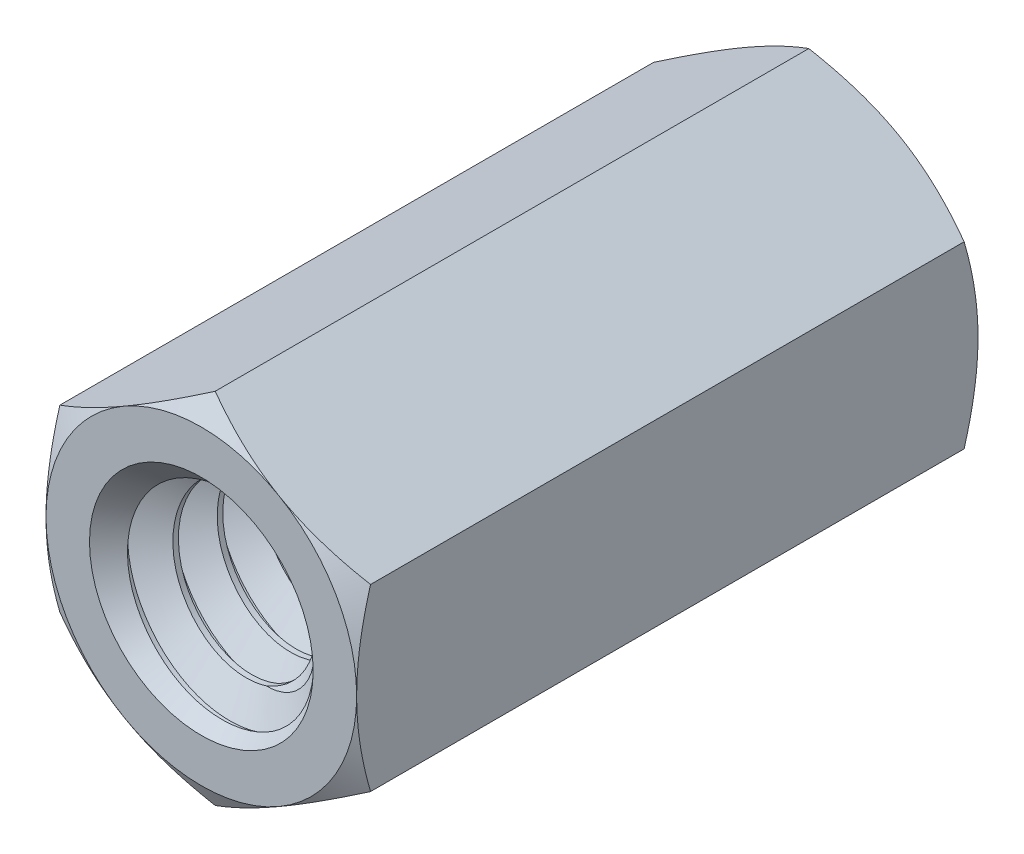
SolidWorks part; units mm, degrees
ref_plane "Front Plane" through (0, 0, 0) normal (0, 0, 1) x (1, 0, 0)
ref_plane "Top Plane" through (0, 0, 0) normal (0, 1, 0) x (1, 0, 0)
ref_plane "Right Plane" through (0, 0, 0) normal (1, 0, 0) x (0, 0, -1)
sketch "Sketch3" plane through (0, 0, 0) normal (1, 0, 0) x (0, 0, -1)
  line L0 (-3.175, 0) -> (3.175, 0) construction
  line L1 (0, 1.5875) -> (0, -1.5875) construction
  line L2 (-3.175, 1.0922) -> (-3.175, -1.0922) construction
  point P2 (-12.7, 0)
  point P3 (12.7, 0)
  dimension "Length" = 6.35
  dimension "Min Thread Length" = 15.875
  dimension "D1" = 15.875
  dimension "Thread Dia" = 2.1844
  dimension "Hex" = 3.175
sketch "Sketch1" plane through (0, 0, 0) normal (0, 0, 1) x (1, 0, 0)
  line L1 (0, 1.8331) -> (-1.5875, 0.9165)
  line L2 (-1.5875, 0.9165) -> (-1.5875, -0.9165)
  line L3 (-1.5875, -0.9165) -> (0, -1.8331)
  line L4 (0, -1.8331) -> (1.5875, -0.9165)
  line L5 (1.5875, -0.9165) -> (1.5875, 0.9165)
  line L6 (1.5875, 0.9165) -> (0, 1.8331)
  circle A0 centre (0, 0) radius 1.5875 construction
  circle A1 centre (0, 0) radius 1.0922
extrude "Extrude1" add sketch "Sketch1" along normal up to vertex (3.175 mm away) and the other way up to vertex (3.175 mm away) up to point (0, 0, 3.175) other way up to point (0, 0, -3.175)
sketch "Sketch11" plane through (0, 0, -3.175) normal (0, 0, -1) x (-1, 0, 0)
  circle A0 centre (0, 0) radius 1.0922 construction
  circle A1 centre (0, 0) radius 1.0922
curve "Helix/Spiral1" pitch 0.4536 height 6.8036 radius 1.0922 centre (0, 0, -3.175) axis (0, 0, 1) start towards (0, 1, 0) parameters "Pitch"=0.4536
sketch "Sketch12" plane through (0, 0, 0) normal (1, 0, 0) x (0, 0, -1)
  line L0 (3.5719, 1.0922) -> (3.175, 1.0922)
  line L1 (3.5719, 1.0922) -> (3.4018, 0.7976)
  line L2 (3.4018, 0.7976) -> (3.3451, 0.7976)
  line L3 (3.3451, 0.7976) -> (3.175, 1.0922)
  line L4 (3.3734, 0.7976) -> (3.3734, 1.0922) construction
  line L5 (3.4868, 0.9449) -> (3.26, 0.9449) construction
  dimension "D1" = 0.0567
  dimension "D2" = 0.2268
  dimension "D3" = 60
sweep "Sweep1" add profiles "Sketch12" path "Helix/Spiral1"
sketch "Sketch6" plane through (0, 0, -3.175) normal (0, 0, -1) x (-1, 0, 0)
  line L6 (0, 1.8331) -> (-1.5875, 0.9165)
  line L7 (-1.5875, 0.9165) -> (-1.5875, -0.9165)
  line L8 (-1.5875, -0.9165) -> (0, -1.8331)
  line L9 (0, -1.8331) -> (1.5875, -0.9165)
  line L10 (1.5875, -0.9165) -> (1.5875, 0.9165)
  line L11 (1.5875, 0.9165) -> (0, 1.8331)
  line L12 (0, 1.8331) -> (-1.5875, 0.9165)
  line L13 (-1.5875, 0.9165) -> (-1.5875, -0.9165)
  line L14 (-1.5875, -0.9165) -> (0, -1.8331)
  line L15 (0, -1.8331) -> (1.5875, -0.9165)
  line L16 (1.5875, -0.9165) -> (1.5875, 0.9165)
  line L17 (1.5875, 0.9165) -> (0, 1.8331)
  dimension "D1" = 0
extrude "Extrude2" cut sketch "Sketch6" along normal through all
sketch "Sketch7" plane through (0, 0, -3.175) normal (0, 0, -1) x (-1, 0, 0)
  circle A2 centre (0, 0) radius 1.143
  circle A3 centre (0, 0) radius 1.143
  dimension "D1" = 0.0508
extrude "Extrude3" cut sketch "Sketch7" against normal through all draft 43
sketch "Sketch8" plane through (0, 0, -3.175) normal (0, 0, -1) x (-1, 0, 0)
  circle A0 centre (0, 0) radius 1.5875 construction
  circle A1 centre (0, 0) radius 1.5875
extrude "Extrude4" cut sketch "Sketch8" against normal through all draft 60 flip side to cut
mirror "Mirror1" about plane through (0, 0, 0) normal (0, 0, 1) of "Extrude2", "Extrude3", "Extrude4"
sketch "Sketch9" [suppressed] plane through (0, 0, 0) normal (1, 0, 0) x (0, 0, -1)
  line L1 (-22.225, 3.2258) -> (22.225, 3.2258)
  line L2 (-22.225, 3.2258) -> (-22.225, 0)
  line L3 (-22.225, 0) -> (22.225, 0)
  line L4 (22.225, 3.2258) -> (22.225, 0)
  line L7 (-38.1, 0) -> (38.1, 0) construction
revolve "Revolve" [suppressed] add sketch "Sketch9" angle 360 about L0
sketch "Sketch10" [suppressed] plane through (0, 0, 0) normal (1, 0, 0) x (0, 0, -1)
  line L0 (38.1, 3.175) -> (22.225, 3.175)
  line L1 (-38.1, 3.175) -> (-22.225, 3.175)
  line L2 (22.225, 3.175) -> (22.225, -3.175)
  line L3 (-38.1, -3.2258) -> (-22.225, -3.2258)
  line L4 (-22.225, 3.175) -> (-22.225, -3.2258)
  line L5 (22.225, -3.175) -> (38.1, -3.175)
equation "\"D1@Sketch3\" = \"Min Thread Length@Sketch3\""
equation "\"D3@Helix/Spiral1\" = \"Length@Sketch3\"+\"Pitch@Helix/Spiral1\""
equation "\"D1@Sketch12\" = \"Pitch@Helix/Spiral1\"*.125"
equation "\"D2@Sketch12\" = \"Pitch@Helix/Spiral1\"*.5"
